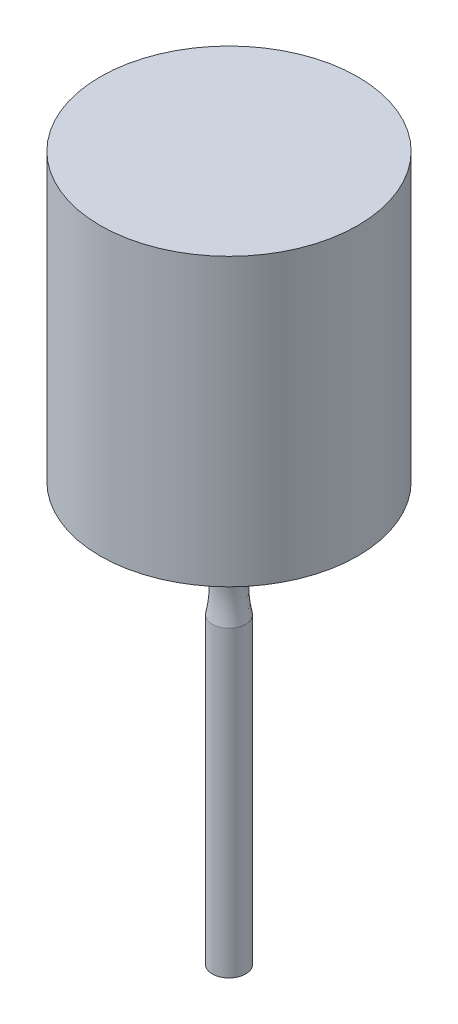
SolidWorks part; units mm, degrees
ref_plane "Front Plane" through (0, 0, 0) normal (0, 0, 1) x (1, 0, 0)
ref_plane "Top Plane" through (0, 0, 0) normal (0, 1, 0) x (1, 0, 0)
ref_plane "Right Plane" through (0, 0, 0) normal (1, 0, 0) x (0, 0, -1)
sketch "Sketch1" plane through (0, 0, 0) normal (0, 1, 0) x (1, 0, 0)
  circle A0 centre (0, 0) radius 27
  dimension "D1" = 54
extrude "Boss-Extrude1" add sketch "Sketch1" along normal blind 60
sketch "Sketch2" plane through (0, 0, 0) normal (0, -1, 0) x (1, 0, 0)
  circle A0 centre (0, 0) radius 22.0345
  circle A1 centre (0, 0) radius 25.527
  dimension "D1" = 44.069
  dimension "D2" = 51.054
extrude "Cut-Extrude1" cut sketch "Sketch2" against normal blind 1.9558
sketch "Sketch3" plane through (0, 0, 0) normal (0, -1, 0) x (1, 0, 0)
  line L0 (0, 0) -> (0, 17) construction
  circle A0 centre (0, 17) radius 2
  circle A1 centre (14.7224, 8.5) radius 2
  circle A2 centre (14.7224, -8.5) radius 2
  circle A3 centre (0, -17) radius 2
  circle A4 centre (-14.7224, -8.5) radius 2
  circle A5 centre (-14.7224, 8.5) radius 2
  point P4 (0, 0)
  point P17 (0, 0)
  dimension "D2" = 4
  dimension "D1" = 17
  dimension "D3" = 6
extrude "Cut-Extrude2" cut sketch "Sketch3" against normal blind 8
sketch "Sketch6" plane through (0, 0, 0) normal (0, -1, 0) x (1, 0, 0)
  circle A0 centre (0, 0) radius 7.62
  dimension "D1" = 15.24
ref_plane "Plane1" through (0, -24.13, 0) normal (0, -1, 0) x (-1, 0, 0)
sketch "Sketch7" plane through (0, -24.13, 0) normal (0, -1, 0) x (-1, 0, 0)
  circle A0 centre (0, 0) radius 3.4925
  dimension "D1" = 6.985
loft "Loft1" add profiles "Sketch7", "Sketch6" connector at (-3.4335, -24.13, 0.6393) connector at (0, 0, -7.62)
sketch "Sketch8" plane through (0, -24.13, 0) normal (0, -1, 0) x (1, 0, 0)
  circle A0 centre (0, 0) radius 3.4925
extrude "Boss-Extrude2" add sketch "Sketch8" along normal blind 63.5
